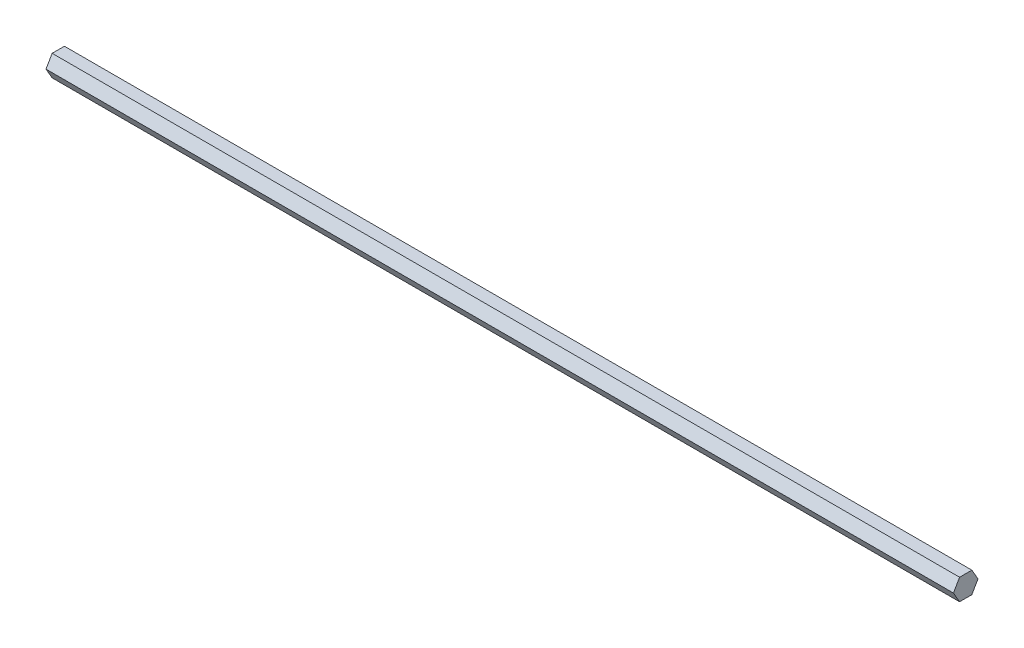
SolidWorks part; units mm, degrees
ref_plane "Front Plane" through (0, 0, 0) normal (0, 0, 1) x (1, 0, 0)
ref_plane "Top Plane" through (0, 0, 0) normal (0, 1, 0) x (1, 0, 0)
ref_plane "Right Plane" through (0, 0, 0) normal (1, 0, 0) x (0, 0, -1)
sketch "Sketch1" plane through (0, 0, 0) normal (1, 0, 0) x (0, 0, -1)
  line L1 (5.4993, 0) -> (2.7496, 4.7625)
  line L2 (2.7496, 4.7625) -> (-2.7496, 4.7625)
  line L3 (-2.7496, 4.7625) -> (-5.4993, 0)
  line L4 (-5.4993, 0) -> (-2.7496, -4.7625)
  line L5 (-2.7496, -4.7625) -> (2.7496, -4.7625)
  line L6 (2.7496, -4.7625) -> (5.4993, 0)
  circle A0 centre (0, 0) radius 4.7625 construction
  dimension "D1" = 9.525
extrude "Boss-Extrude1" add sketch "Sketch1" along normal blind 406.4
ref_axis "Axis3" through (426.72, 0, 0) along (-1, 0, 0)
